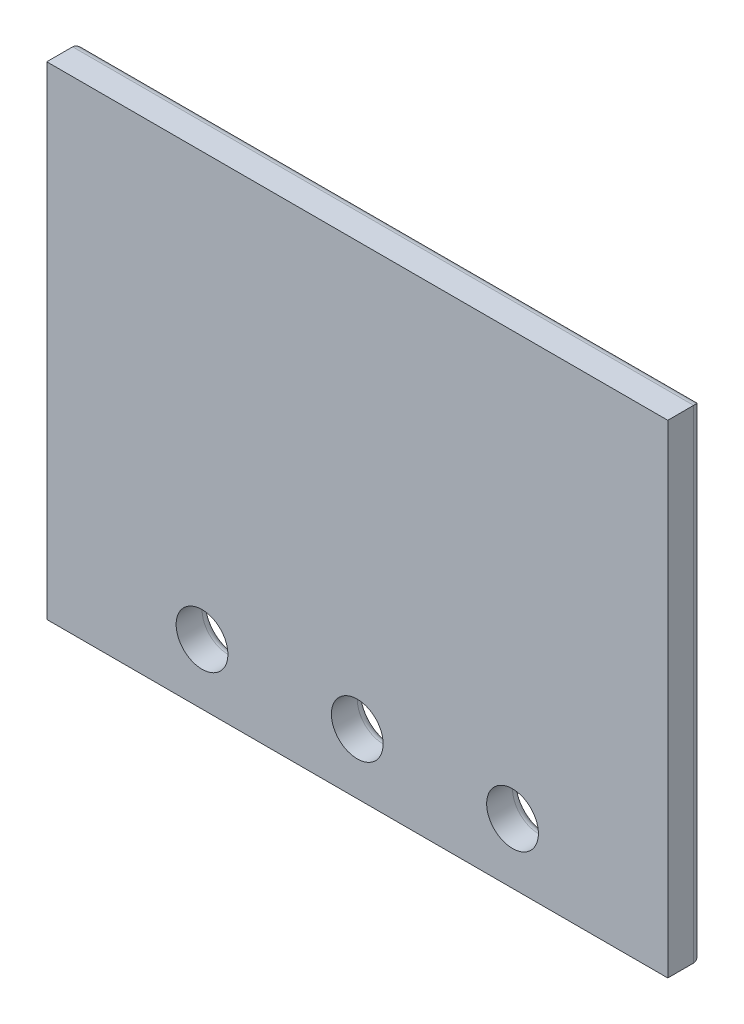
SolidWorks part; units mm, degrees
ref_plane "Piano frontale" through (0, 0, 0) normal (0, 0, 1) x (1, 0, 0)
ref_plane "Piano superiore" through (0, 0, 0) normal (0, 1, 0) x (1, 0, 0)
ref_plane "Piano destro" through (0, 0, 0) normal (1, 0, 0) x (0, 0, -1)
sketch "Schizzo1" plane through (0, 0, 0) normal (0, 0, 1) x (1, 0, 0)
  line L1 (-180, 140) -> (180, 140)
  line L2 (-180, 140) -> (-180, -140)
  line L3 (-180, -140) -> (180, -140)
  line L4 (180, 140) -> (180, -140)
  line L5 (-180, 140) -> (180, -140) construction
  line L6 (-180, -140) -> (180, 140) construction
  circle A0 centre (-90, -105) radius 15
  circle A1 centre (90, -105) radius 15
  circle A2 centre (0, -105) radius 15
  point P0 (0, 0)
  dimension "D3" = 30
  dimension "D4" = 30
  dimension "D5" = 30
  dimension "D1" = 360
  dimension "D2" = 280
extrude "Estrusione-Estrusione1" add sketch "Schizzo1" along normal blind 20
sketch "Schizzo2" plane through (0, 0, 0) normal (0, 0, -1) x (-1, 0, 0)
  line L0 (0, -140) -> (0, 0) construction
  line L1 (180, -140) -> (-180, -140) construction
  line L2 (-75, -70) -> (75, -70)
  line L3 (-75, -70) -> (-75, -40)
  line L4 (-75, -40) -> (75, -40)
  line L5 (75, -40) -> (75, -70)
  point P8 (0, -70)
extrude "Estrusione-Estrusione2" add sketch "Schizzo2" along normal blind 60
sketch "Schizzo3" plane through (0, -70, 0) normal (0, -1, 0) x (1, 0, 0)
  line L6 (60, 0) -> (-60, 0)
  line L9 (60, 0) -> (60, -45)
  line L10 (-60, -45) -> (-60, 0)
  line L11 (60, -45) -> (-60, -45)
  line L12 (60, 0) -> (60, -45)
  line L13 (-60, -45) -> (-60, 0)
  line L14 (60, -45) -> (-60, -45)
  dimension "D1" = 15
extrude "Taglio-Estrusione2" cut sketch "Schizzo3" against normal up to surface (30 mm away) up to face at (0, -40, -30)
fillet "Raccordo2" radius 10 4 edges at (-75, -55, -60) (0, -40, -60) (75, -55, -60) (0, -70, -60)
fillet "Raccordo3" radius 10 1 edges at (60, -55, -45)
fillet "Raccordo4" radius 10 1 edges at (-60, -55, -45)
fillet "Raccordo5" radius 10 2 edges at (75, -70, -25) (72.0711, -67.0711, -57.0711)
fillet "Raccordo6" radius 10 2 edges at (-75, -40, -25) (-72.0711, -42.9289, -57.0711)
fillet "Raccordo7" radius 10 2 edges at (75, -40, -25) (72.0711, -42.9289, -57.0711)
fillet "Raccordo8" radius 10 2 edges at (-75, -70, -25) (-72.0711, -67.0711, -57.0711)
fillet "Raccordo12" radius 5 19 edges at (-72.0711, -42.9289, 0) (-62.5, -40, 0) (-60, -55, 0) (-62.5, -70, 0) (-72.0711, -67.0711, 0) (-75, -55, 0) (0, 140, 0) (-180, 0, 0) (0, -140, 0) (180, 0, 0) (-75, -105, 0) (105, -105, 0) (15, -105, 0) (72.0711, -42.9289, 0) (75, -55, 0) (72.0711, -67.0711, 0) (62.5, -70, 0) (60, -55, 0) (62.5, -40, 0)
